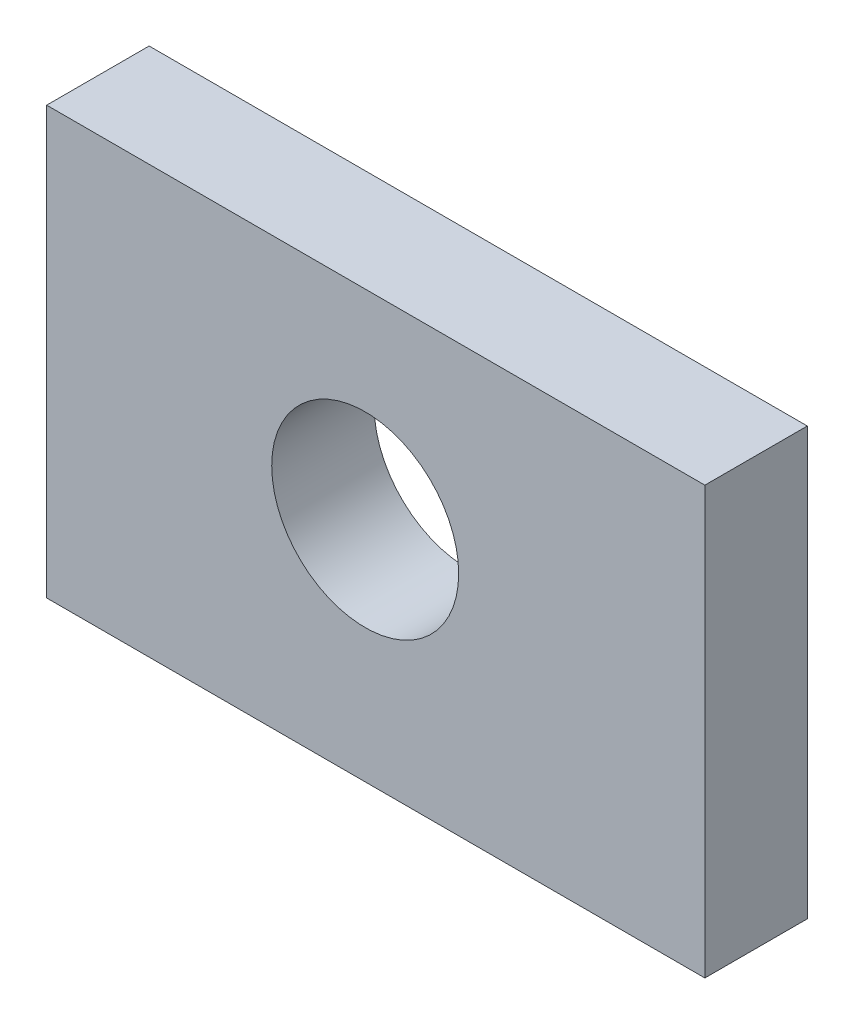
SolidWorks part; units mm, degrees
material "Клен"
ref_plane "Спереди" through (0, 0, 0) normal (0, 0, 1) x (1, 0, 0)
ref_plane "Сверху" through (0, 0, 0) normal (0, 1, 0) x (1, 0, 0)
ref_plane "Справа" through (0, 0, 0) normal (1, 0, 0) x (0, 0, -1)
sketch "Эскиз1" plane through (0, 0, 0) normal (0, 0, 1) x (1, 0, 0)
  line L1 (-15.2546, 6.0784) -> (23.2954, 6.0784)
  line L2 (-15.2546, 6.0784) -> (-15.2546, 31.0784)
  line L3 (-15.2546, 31.0784) -> (23.2954, 31.0784)
  line L4 (23.2954, 6.0784) -> (23.2954, 31.0784)
  line L5 (23.2954, 0.0784) -> (23.2954, 6.0784) construction
  line L6 (-15.2546, 6.0784) -> (-15.2546, 0.0784) construction
  circle A0 centre (4.6404, 19.3784) radius 6.3159
  point P9 (-15.2546, 3.0784)
  dimension "D1" = 25
extrude "Бобышка-Вытянуть1" add sketch "Эскиз1" along normal blind 6 contours L2 L3 L4 L1
sketch "Эскиз2" plane through (0, 0, 6) normal (0, 0, 1) x (1, 0, 0)
  circle A0 centre (3.4004, 19.3784) radius 5.475
  point P2 (4.6404, 19.3784)
  point P3 (3.4004, 19.3784)
  dimension "D1" = 10.95
extrude "Вырез-Вытянуть1" cut sketch "Эскиз2" against normal through all
